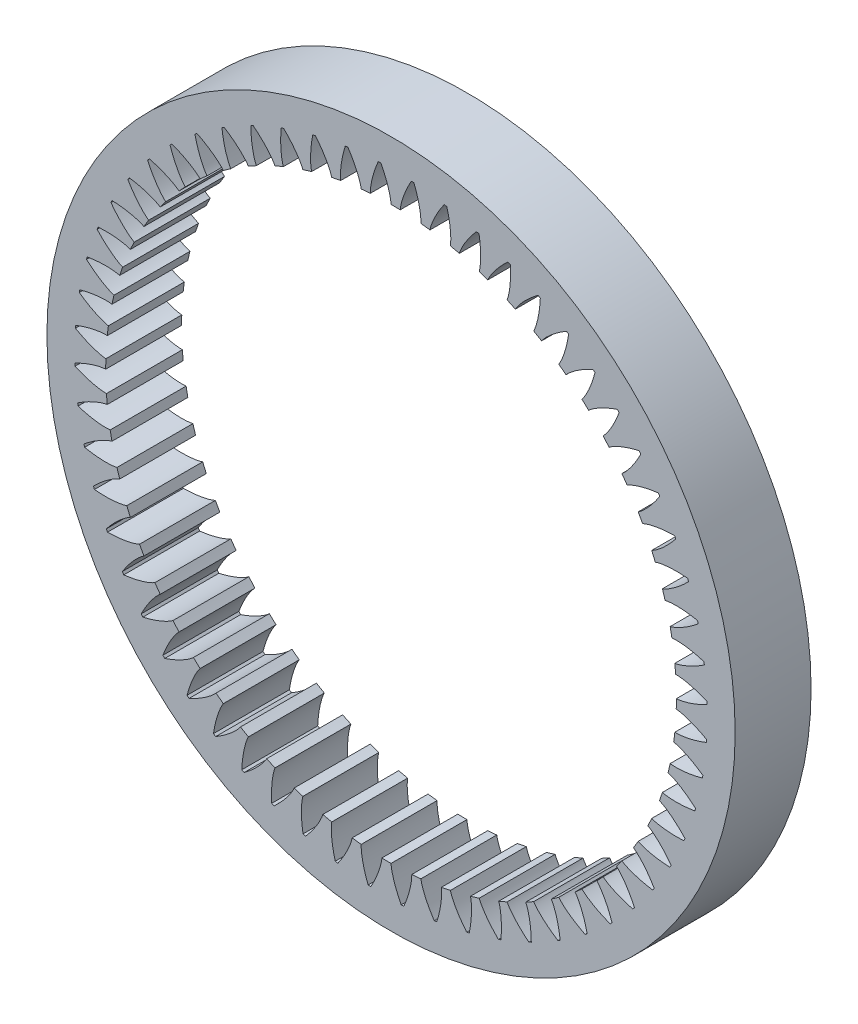
SolidWorks part; units mm, degrees
ref_plane "Front Plane" through (0, 0, 0) normal (0, 0, 1) x (1, 0, 0)
ref_plane "Top Plane" through (0, 0, 0) normal (0, 1, 0) x (1, 0, 0)
ref_plane "Right Plane" through (0, 0, 0) normal (1, 0, 0) x (0, 0, -1)
sketch "Sketch1" plane through (0, 0, 0) normal (0, 0, 1) x (1, 0, 0)
  circle A0 centre (0, 0) radius 68
  circle A1 centre (0, 0) radius 56.38
  dimension "D1" = 136
  dimension "D2" = 112.76
extrude "Boss-Extrude2" add sketch "Sketch1" along normal blind 15
sketch "Sketch3" plane through (0, 0, 0) normal (0, 0, 1) x (1, 0, 0)
  line L0 (0, 0) -> (62.4587, 2.2715) construction
  circle A0 centre (0, 0) radius 58
  circle A3 centre (0, 0) radius 62.5
  arc A4 (56.2311, 4.0955) -> (56.38, 0) centre (0, 0) cw
  circle A5 centre (0, 0) radius 56.38 construction
  arc A6 (62.4487, 2.5319) -> (62.4676, 2.0111) centre (0, 0) cw
  spline S0 degree 4 poles (56.38, 0) (56.3904, 0.0001) (56.4196, 0.0008) (56.4749, 0.0033) (56.565, 0.0095) (56.6798, 0.0201) (56.8281, 0.037) (57.0028, 0.0612) (57.1945, 0.0921) (57.403, 0.1304) (57.6109, 0.1728) (57.818, 0.2189) (58.0242, 0.2684) (58.2738, 0.3324) (58.5727, 0.415) (58.9215, 0.5198) (59.3165, 0.6486) (59.7182, 0.7904) (60.1129, 0.9387) (60.5108, 1.0984) (60.8953, 1.26) (61.2936, 1.4381) (61.6608, 1.6077) (62.0712, 1.809) (62.402, 1.9748) (62.8371, 2.2054) (63.0937, 2.3453) (63.3936, 2.5131) (63.5265, 2.5898) (63.6083, 2.6369) knots 0 0 0 0 0 0.005377 0.015084 0.028532 0.04661 0.064855 0.092111 0.119476 0.146842 0.174209 0.201575 0.228941 0.256307 0.307035 0.361767 0.4165 0.471232 0.525964 0.580697 0.635429 0.690161 0.744894 0.799626 0.854358 0.909091 0.954545 1 1 1 1 1 construction
  spline S1 degree 4 poles (56.38, 0) (56.3904, 0.0001) (56.4196, 0.0008) (56.4749, 0.0033) (56.565, 0.0095) (56.6798, 0.0201) (56.8281, 0.037) (57.0028, 0.0612) (57.1945, 0.0921) (57.403, 0.1304) (57.6109, 0.1728) (57.818, 0.2189) (58.0242, 0.2684) (58.2738, 0.3324) (58.5727, 0.415) (58.9215, 0.5198) (59.3165, 0.6486) (59.7182, 0.7904) (60.1129, 0.9387) (60.5108, 1.0984) (60.8953, 1.26) (61.2936, 1.4381) (61.6608, 1.6077) (62.0306, 1.7891) (62.2529, 1.9001) (62.4077, 1.9799) (62.4676, 2.0111) knots 0 0 0 0 0 0.005377 0.015084 0.028532 0.04661 0.064855 0.092111 0.119476 0.146842 0.174209 0.201575 0.228941 0.256307 0.307035 0.361767 0.4165 0.471232 0.525964 0.580697 0.635429 0.690161 0.744894 0.799626 0.832728 0.832728 0.832728 0.832728 0.832728
  spline S2 degree 4 poles (56.2311, 4.0955) (56.2415, 4.0961) (56.2707, 4.0976) (56.3259, 4.099) (56.4163, 4.0995) (56.5315, 4.0972) (56.6807, 4.0911) (56.8566, 4.0797) (57.0501, 4.0628) (57.2609, 4.0398) (57.4712, 4.0126) (57.6812, 3.9816) (57.8904, 3.9473) (58.144, 3.9015) (58.4481, 3.8409) (58.8036, 3.7616) (59.2069, 3.6619) (59.6179, 3.5496) (60.0223, 3.4305) (60.4308, 3.3001) (60.8259, 3.1668) (61.2362, 3.0181) (61.6147, 2.8756) (61.9967, 2.7216) (62.2265, 2.627) (62.3867, 2.5587) (62.4487, 2.5319) knots 0 0 0 0 0 0.005377 0.015084 0.028532 0.04661 0.064855 0.092111 0.119476 0.146842 0.174209 0.201575 0.228941 0.256307 0.307035 0.361767 0.4165 0.471232 0.525964 0.580697 0.635429 0.690161 0.744894 0.799626 0.832728 0.832728 0.832728 0.832728 0.832728
extrude "Cut-Extrude3" cut sketch "Sketch3" along normal blind 15 contours S2 A4 S1 A0 | S2 A0 S1 A3 region at (57.1264, 2.0776, 0) region at (59.6856, 2.1707, 0)
pattern_circular "CirPattern1" count 60 over 360 about axis through (0, 0, 15) along (0, 0, 1) of "Cut-Extrude3"
